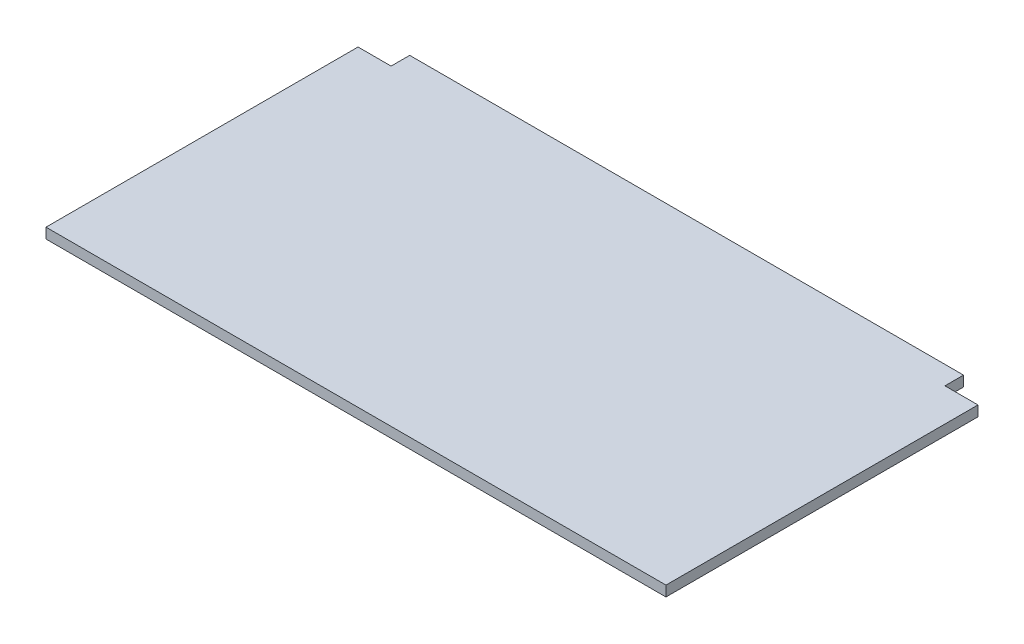
SolidWorks part; units mm, degrees
material "Cedar"
ref_plane "Front Plane" through (0, 0, 0) normal (0, 0, 1) x (1, 0, 0)
ref_plane "Top Plane" through (0, 0, 0) normal (0, 1, 0) x (1, 0, 0)
ref_plane "Right Plane" through (0, 0, 0) normal (1, 0, 0) x (0, 0, -1)
sketch "Sketch1" plane through (0, 0, 0) normal (0, 1, 0) x (1, 0, 0)
  line L1 (750, -400) -> (-750, -400)
  line L2 (750, -400) -> (750, 400)
  line L3 (750, 400) -> (-750, 400)
  line L4 (-750, -400) -> (-750, 400)
  line L5 (750, -400) -> (-750, 400) construction
  line L6 (750, 400) -> (-750, -400) construction
  point P0 (0, 0)
  dimension "D1" = 800
  dimension "D2" = 1500
extrude "RawMaterial" add sketch "Sketch1" along normal blind 25
sketch "Sketch2" plane through (0, 25, 0) normal (0, 1, 0) x (1, 0, 0)
  line L0 (750, 400) -> (-750, 400) construction
  line L1 (-761.4719, 422.6992) -> (-670, 422.6992)
  line L2 (-761.4719, 422.6992) -> (-761.4719, 355)
  line L3 (-761.4719, 355) -> (-670, 355)
  line L4 (-670, 422.6992) -> (-670, 355)
  line L5 (777.3454, 416.3957) -> (670, 416.3957)
  line L6 (777.3454, 416.3957) -> (777.3454, 355)
  line L7 (777.3454, 355) -> (670, 355)
  line L8 (670, 416.3957) -> (670, 355)
  line L9 (-750, 400) -> (-750, -400) construction
  line L10 (750, -400) -> (750, 400) construction
  line M5 (-750, 400) -> (-750, -400)
  line M7 (750, -400) -> (750, 400)
  line M8 (750, 400) -> (-750, 400)
  dimension "D1" = 45
  dimension "D2" = 80
  dimension "D3" = 80
extrude "SlotsForFrame" cut sketch "Sketch2" against normal through all contours L4 L3 M8 M5 | L8 L7 M8 M7 region at (710, 25, -377.5) region at (-710, 25, -377.5)
equation "\"D3@Sketch2\"=\"D2@Sketch2\""
equation "\"TableThickness\"= \"Thickness@RawMaterial\""
